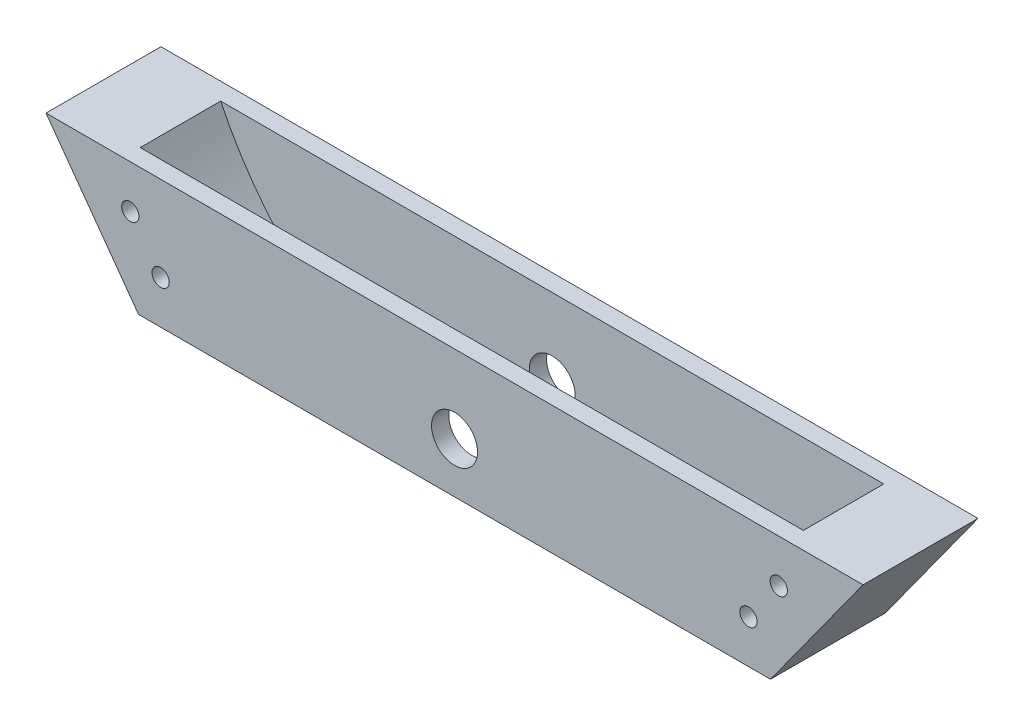
SolidWorks part; units mm, degrees
ref_plane "Front Plane" through (0, 0, 0) normal (0, 0, 1) x (1, 0, 0)
ref_plane "Top Plane" through (0, 0, 0) normal (0, 1, 0) x (1, 0, 0)
ref_plane "Right Plane" through (0, 0, 0) normal (1, 0, 0) x (0, 0, -1)
sketch "Sketch1" plane through (0, 0, 0) normal (0, 0, 1) x (1, 0, 0)
  line L0 (0, 0) -> (0, -62.5) construction
  line L1 (-71.0874, -27.7045) -> (0, -27.7045) construction
  line L2 (0, -50) -> (-54.9811, -50) construction
  line L3 (-54.9811, -50) -> (-71.0874, -27.7045) construction
  line L4 (-56.4171, -35.2045) -> (-51.1468, -42.5) construction
  line L5 (-71.0874, -27.7045) -> (-54.9811, -50)
  line L6 (-54.9811, -50) -> (-39.95, -50)
  line L7 (-71.0874, -27.7045) -> (-57.6928, -27.7045)
  line L8 (54.9811, -50) -> (39.95, -50)
  line L9 (71.0874, -27.7045) -> (54.9811, -50)
  line L10 (71.0874, -27.7045) -> (57.6928, -27.7045)
  circle A0 centre (0, 0) radius 62.5 construction
  circle A2 centre (0, -41.25) radius 4
  circle A3 centre (-56.4171, -35.2045) radius 4 construction
  circle A4 centre (-51.1468, -42.5) radius 4 construction
  circle A5 centre (-56.4171, -35.2045) radius 1.5
  circle A6 centre (-51.1468, -42.5) radius 1.5
  circle A7 centre (0, -41.25) radius 15
  circle A8 centre (0, 0) radius 55.5 construction
  circle A9 centre (0, 0) radius 56.25 construction
  circle A10 centre (0, 0) radius 64 construction
  arc A11 (-57.6928, -27.7045) -> (-39.95, -50) centre (0, 0) ccw
  arc A12 (57.6928, -27.7045) -> (39.95, -50) centre (0, 0) cw
  circle A13 centre (51.1468, -42.5) radius 1.5
  circle A14 centre (56.4171, -35.2045) radius 1.5
  point P20 (0, 0)
  point P24 (0, 0)
  point P25 (0, 0)
  point P26 (0, 0)
  point P27 (-41.4695, -50)
  point P28 (-39.95, -50)
  point P29 (-40.1655, -50)
  dimension "D1" = 125
  dimension "D3" = 8
  dimension "D4" = 8
  dimension "D9" = 3
  dimension "D11" = 30
  dimension "D12" = 112.5
  dimension "D13" = 128
  dimension "D5" = 9
  dimension "D6" = 20
  dimension "D7" = 7.5
  dimension "D8" = 7.5
  dimension "D10" = 7.5
  dimension "D2" = 7
extrude "Boss-Extrude1" add sketch "Sketch1" along normal mid plane 14 contours A11 L7 L5 L6 A6 A5 | L10 A12 L8 L9 A13 A14 region at (-56.5922, -39.0563, 0) region at (56.5922, -39.0563, 0)
sketch "Sketch2" plane through (0, 0, 7) normal (0, 0, 1) x (1, 0, 0)
  line L0 (-54.9811, -50) -> (54.9811, -50)
  line L1 (54.9811, -50) -> (71.0874, -27.7045)
  line L2 (71.0874, -27.7045) -> (-71.0874, -27.7045)
  line L3 (-71.0874, -27.7045) -> (-54.9811, -50)
  circle A0 centre (0, -41.25) radius 4 construction
  circle A1 centre (0, -41.25) radius 4
  circle A2 centre (56.4171, -35.2045) radius 1.5 construction
  circle A3 centre (51.1468, -42.5) radius 1.5 construction
  circle A4 centre (-51.1468, -42.5) radius 1.5 construction
  circle A5 centre (-56.4171, -35.2045) radius 1.5 construction
  circle A6 centre (56.4171, -35.2045) radius 1.5
  circle A7 centre (51.1468, -42.5) radius 1.5
  circle A8 centre (-51.1468, -42.5) radius 1.5
  circle A9 centre (-56.4171, -35.2045) radius 1.5
extrude "Boss-Extrude2" add sketch "Sketch2" along normal blind 3
mirror "Mirror2" about plane through (0, 0, 0) normal (0, 0, 1) of "Boss-Extrude2"
equation "\"D12@Sketch1\"=75*1.5"
equation "\"D11@Sketch1\"=20*1.5"
